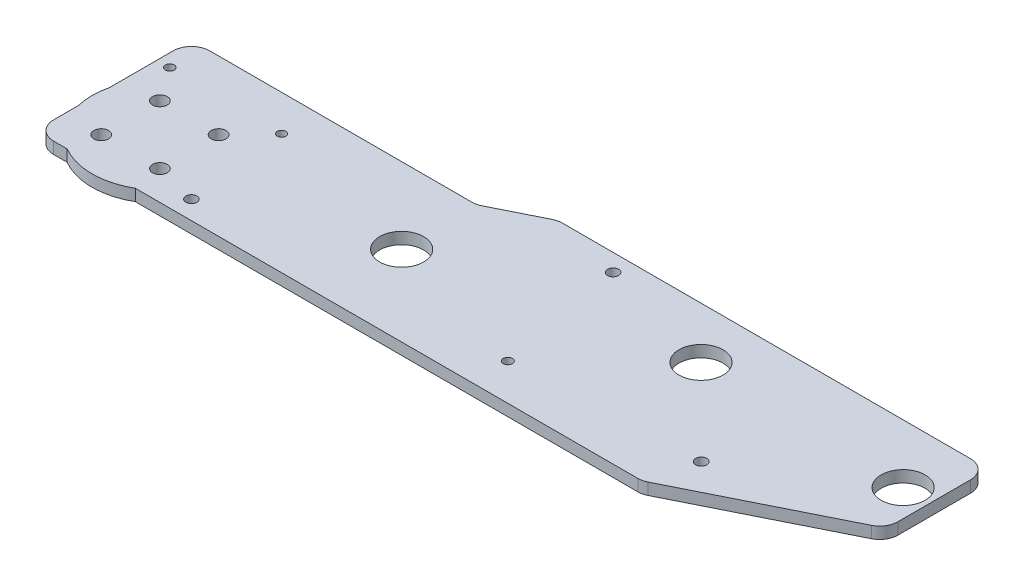
SolidWorks part; units mm, degrees
ref_plane "Front" through (0, 0, 0) normal (0, 0, 1) x (1, 0, 0)
ref_plane "Top" through (0, 0, 0) normal (0, 1, 0) x (1, 0, 0)
ref_plane "Right" through (0, 0, 0) normal (1, 0, 0) x (0, 0, -1)
sketch "Sketch1" plane through (0, 0, 0) normal (0, 1, 0) x (1, 0, 0)
  line L1 (0, 0) -> (210, 0)
  line L2 (0, 0) -> (0, -50)
  line L3 (0, -50) -> (210, -50)
  line L4 (210, 0) -> (210, -50)
  circle A7 centre (3.4895, -16.7877) radius 1.2117
  circle A8 centre (34.3726, -17.194) radius 1.1656
  circle A9 centre (37.5207, -44.9212) radius 1.5
  circle A10 centre (118.879, -40.0177) radius 1.25
  circle A11 centre (112.3021, -4.7393) radius 1.5
  circle A12 centre (168.9752, -37.4032) radius 1.5173
  dimension "D1" = 210
  dimension "D2" = 50
extrude "Boss-Extrude1" add sketch "Sketch1" along normal blind 3.175
sketch "Sketch2" plane through (0, 3.175, 0) normal (0, 1, 0) x (1, 0, 0)
  line L0 (210, 0) -> (0, 0) construction
  line L1 (0, 0) -> (0, -50) construction
  circle A0 centre (10, -26) radius 2
  circle A1 centre (10, -42) radius 2
  circle A2 centre (26, -26) radius 2
  circle A3 centre (26, -42) radius 2
  dimension "D1" = 16
  dimension "D2" = 16
  dimension "D3" = 16
  dimension "D4" = 26
  dimension "D5" = 10
  dimension "D6" = 10
  dimension "D7" = 26
  dimension "D8" = 16
extrude "Cut-Extrude1" cut sketch "Sketch2" against normal blind 10
sketch "Sketch3" plane through (0, 3.175, 0) normal (0, 1, 0) x (1, 0, 0)
  line L0 (210, 0) -> (0, 0) construction
  line L1 (210, 0) -> (0, 0) construction
  circle A0 centre (78.0103, -28.1) radius 6
  circle A1 centre (145.5313, -14) radius 6
  circle A2 centre (18, -34) radius 0.587
  circle A3 centre (26, -26) radius 2 construction
  circle A4 centre (202.6463, -16) radius 6
  dimension "D1" = 28.1
  dimension "D3" = 16
  dimension "D4" = 14
  dimension "D7" = 125.222
  dimension "D2" = 60.2996
  dimension "D5" = 8
  dimension "D6" = 8
  dimension "D8" = 57.15
extrude "Cut-Extrude2" cut sketch "Sketch3" against normal blind 57.15
sketch "Sketch4" [suppressed] plane through (0, 3.175, 0) normal (0, 1, 0) x (1, 0, 0)
  line L0 (3.4895, -16.7877) -> (18, -34)
  line L1 (3.4895, -20.6627) -> (5.9498, -23.5811)
  line L2 (18, -34) -> (34.3726, -17.194)
  line L3 (34.3726, -17.194) -> (75.8499, -28.1)
  line L4 (75.8499, -28.1) -> (37.5207, -44.9212)
  line L5 (7.3432, -17.194) -> (9.8664, -20.303)
  circle A0 centre (18, -34) radius 15.9299
  circle A1 centre (3.4895, -16.7877) radius 3.8751
  circle A2 centre (34.3726, -17.194) radius 3.7227
  circle A3 centre (37.5207, -44.9212) radius 3.8676
  circle A4 centre (75.8499, -28.1) radius 12.797
  circle A5 centre (112.3021, -4.7393) radius 5.1588
  circle A6 centre (118.879, -40.0177) radius 4.9035
  circle A7 centre (140.772, -16) radius 12.6375
  circle A8 centre (168.9752, -37.4032) radius 4.2066
  circle A9 centre (197.922, -16) radius 12.8
sketch "Sketch5" [suppressed] plane through (0, 3.175, 0) normal (0, 1, 0) x (1, 0, 0)
  line L0 (210, 0) -> (0, 0) construction
  line L2 (-0.6266, -16.7877) -> (37.5207, -16.7877)
  line L3 (-0.6266, -16.7877) -> (-0.6266, -44.9212)
  line L4 (-0.6266, -44.9212) -> (37.5207, -44.9212)
  line L5 (37.5207, -16.7877) -> (37.5207, -44.9212)
  line L6 (75.8499, -15.182) -> (37.5207, -15.182)
  line L7 (75.8499, -15.182) -> (75.8499, -44.9212)
  line L8 (75.8499, -44.9212) -> (37.5207, -44.9212)
  line L9 (37.5207, -15.182) -> (37.5207, -44.9212)
  line L10 (112.3021, -4.7393) -> (75.8499, -4.7393)
  line L11 (112.3021, -4.7393) -> (112.3021, -44.9212)
  line L12 (112.3021, -44.9212) -> (75.8499, -44.9212)
  line L13 (75.8499, -4.7393) -> (75.8499, -44.9212)
  line L14 (112.3021, -4.7393) -> (102.3945, -4.7393)
  line L16 (112.3021, -4.7393) -> (112.3021, 0)
  line L17 (112.3021, 0) -> (102.3945, 0)
  line L18 (102.3945, -4.7393) -> (102.3945, 0)
  line L19 (210, -50) -> (210, 0) construction
  line L20 (112.3021, -4.7393) -> (123.1553, -4.7393)
  line L21 (112.3021, -4.7393) -> (112.3021, 0)
  line L22 (112.3021, 0) -> (123.1553, 0)
  line L23 (123.1553, -4.7393) -> (123.1553, 0)
  line L24 (112.3021, -4.7393) -> (140.772, -4.7393)
  line L25 (112.3021, -4.7393) -> (112.3021, -40.0177)
  line L26 (112.3021, -40.0177) -> (140.772, -40.0177)
  line L27 (140.772, -4.7393) -> (140.772, -40.0177)
  line L28 (140.772, -16) -> (168.9752, -16)
  line L29 (140.772, -16) -> (140.772, -40.0177)
  line L30 (140.772, -40.0177) -> (168.9752, -40.0177)
  line L31 (168.9752, -16) -> (168.9752, -40.0177)
  line L32 (168.9752, -4.7393) -> (210, -4.7393)
  line L33 (168.9752, -4.7393) -> (168.9752, -40.0177)
  line L34 (168.9752, -40.0177) -> (210, -40.0177)
  line L35 (210, -4.7393) -> (210, -40.0177)
  line L36 (0, -50) -> (210, -50) construction
  line L37 (160.7629, -40.0177) -> (177.2091, -40.0177)
  line L38 (160.7629, -40.0177) -> (160.7629, -44.9212)
  line L39 (160.7629, -44.9212) -> (177.2091, -44.9212)
  line L40 (177.2091, -40.0177) -> (177.2091, -44.9212)
  line L41 (112.3021, -40.0177) -> (126.3591, -40.0177)
  line L42 (112.3021, -40.0177) -> (112.3021, -47.7828)
  line L43 (112.3021, -47.7828) -> (126.3591, -47.7828)
  line L44 (126.3591, -40.0177) -> (126.3591, -47.7828)
  line L45 (30.5963, -44.9212) -> (44.6115, -44.9212)
  line L46 (30.5963, -44.9212) -> (30.5963, -50)
  line L47 (30.5963, -50) -> (44.6115, -50)
  line L48 (44.6115, -44.9212) -> (44.6115, -50)
  line L50 (-0.6266, -44.9212) -> (30.5963, -44.9212)
  line L51 (-0.6266, -44.9212) -> (-0.6266, -50)
  line L52 (-0.6266, -50) -> (30.5963, -50)
  line L53 (30.5963, -44.9212) -> (30.5963, -50)
  circle A0 centre (3.4895, -16.7877) radius 4.1161
  circle A1 centre (34.3726, -17.194) radius 3.8132
  circle A2 centre (75.8499, -28.1) radius 12.918
  circle A3 centre (112.3021, -4.7393) radius 5.2663
  circle A4 centre (140.772, -16) radius 13.0245
  circle A5 centre (197.922, -16) radius 12.3805
  circle A6 centre (168.9752, -37.4032) radius 4.7643
  circle A7 centre (118.879, -40.0177) radius 5.279
  circle A8 centre (37.5207, -44.9212) radius 4.2049
  line M12 (0, 0) -> (0, -50)
  line M13 (0, -50) -> (210, -50)
  line M14 (210, -50) -> (210, 0)
  line M15 (210, 0) -> (0, 0)
extrude "Cut-Extrude5" [suppressed] cut sketch "Sketch5" against normal blind 11.52 contours A5 L32 L23 L24 A4 L28 L33 M14 M15 | A1 L6 L13 L10 L18 A0 L2 M15 M12 | L8 L48 L34 L40 L39 L38 L30 L26 L44 L43 L42 L12 M13 M14
fillet "Fillet1" [suppressed] radius 5
sketch "Sketch10" plane through (0, 3.175, 0) normal (0, 1, 0) x (1, 0, 0)
  line L0 (210, -27.8594) -> (165.5029, -50)
  line L1 (210, -50) -> (210, 0) construction
  line L2 (0, -50) -> (210, -50) construction
  line L3 (165.5029, -50) -> (210, -50)
  line L4 (210, -50) -> (210, -27.8594)
  line L5 (92.5326, 0) -> (77.6548, -7.4028)
  line L6 (210, 0) -> (0, 0) construction
  line L7 (77.6548, -7.4028) -> (0, -7.4028)
  line L8 (0, 0) -> (0, -50) construction
  line L9 (0, -7.4028) -> (0, 0)
  line L10 (0, 0) -> (92.5326, 0)
extrude "Cut-Extrude7" cut sketch "Sketch10" against normal blind 10
fillet "Fillet3" radius 5 7 edges at (0, 1.5875, 50) (0, 1.5875, 7.4028) (77.6548, 1.5875, 7.4028) (92.5326, 1.5875, 0) (210, 1.5875, 0) (210, 1.5875, 27.8594) (165.5029, 1.5875, 50)
sketch "Sketch11" plane through (0, 3.175, 0) normal (0, 1, 0) x (1, 0, 0)
  circle A0 centre (18, -34) radius 18.5
  circle A1 centre (10, -26) radius 2
  circle A2 centre (10, -42) radius 2
  circle A3 centre (26, -26) radius 2
  circle A4 centre (26, -42) radius 2
extrude "Boss-Extrude4" add sketch "Sketch11" against normal blind 3.175
